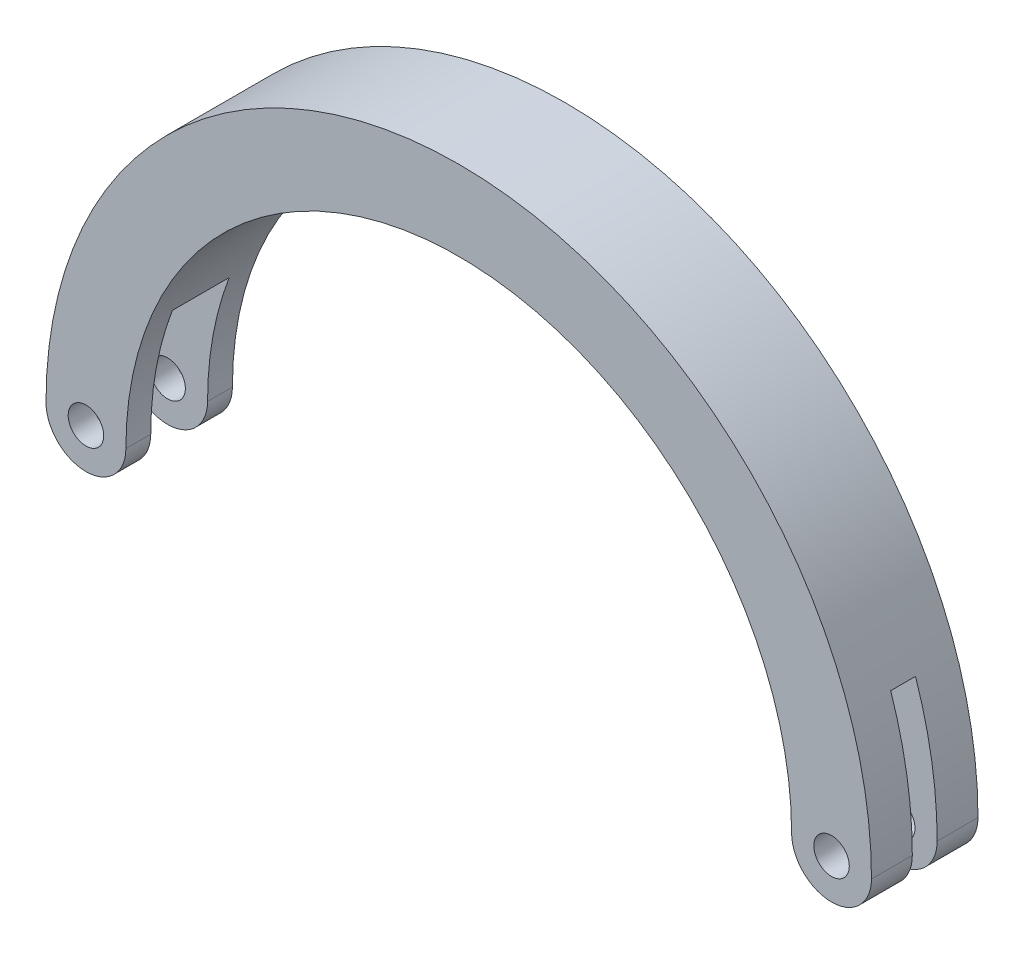
SolidWorks part; units mm, degrees
ref_plane "Front Plane" through (0, 0, 0) normal (0, 0, 1) x (1, 0, 0)
ref_plane "Top Plane" through (0, 0, 0) normal (0, 1, 0) x (1, 0, 0)
ref_plane "Right Plane" through (0, 0, 0) normal (1, 0, 0) x (0, 0, -1)
sketch "Sketch1" plane through (0, 0, 0) normal (0, 0, 1) x (1, 0, 0)
  line L0 (0, 0) -> (42, 0) construction
  circle A0 centre (0, 0) radius 1
  circle A1 centre (42, 0) radius 1
  circle A2 centre (0, 0) radius 2.25
  circle A3 centre (42, 0) radius 2.25
  arc A4 (2.25, 0) -> (39.75, 0) centre (21, 0) cw
  arc A5 (-2.25, 0) -> (44.25, 0) centre (21, 0) cw
  dimension "D1" = 2
  dimension "D2" = 2
  dimension "D4" = 4.5
  dimension "D5" = 4.5
  dimension "D3" = 42
extrude "Boss-Extrude1" add sketch "Sketch1" along normal blind 3 and the other way blind 3 contours A0 A2 | A5 A2 A4 A3 | A3 A1 region at (0, -2.1864, 0) region at (0, 2.7699, 0) region at (42, 2.1864, 0)
sketch "Sketch2" plane through (0, 0, 0) normal (0, 0, 1) x (1, 0, 0)
  circle A0 centre (0, 0) radius 7.5
  dimension "D1" = 15
extrude "Cut-Extrude1" cut sketch "Sketch2" against normal blind 1.6 and the other way blind 1.6
sketch "Sketch3" plane through (0, 0, 0) normal (0, 0, 1) x (1, 0, 0)
  circle A0 centre (42, 0) radius 7.5
  dimension "D1" = 15
extrude "Cut-Extrude2" cut sketch "Sketch3" against normal blind 0.7 and the other way blind 0.7
